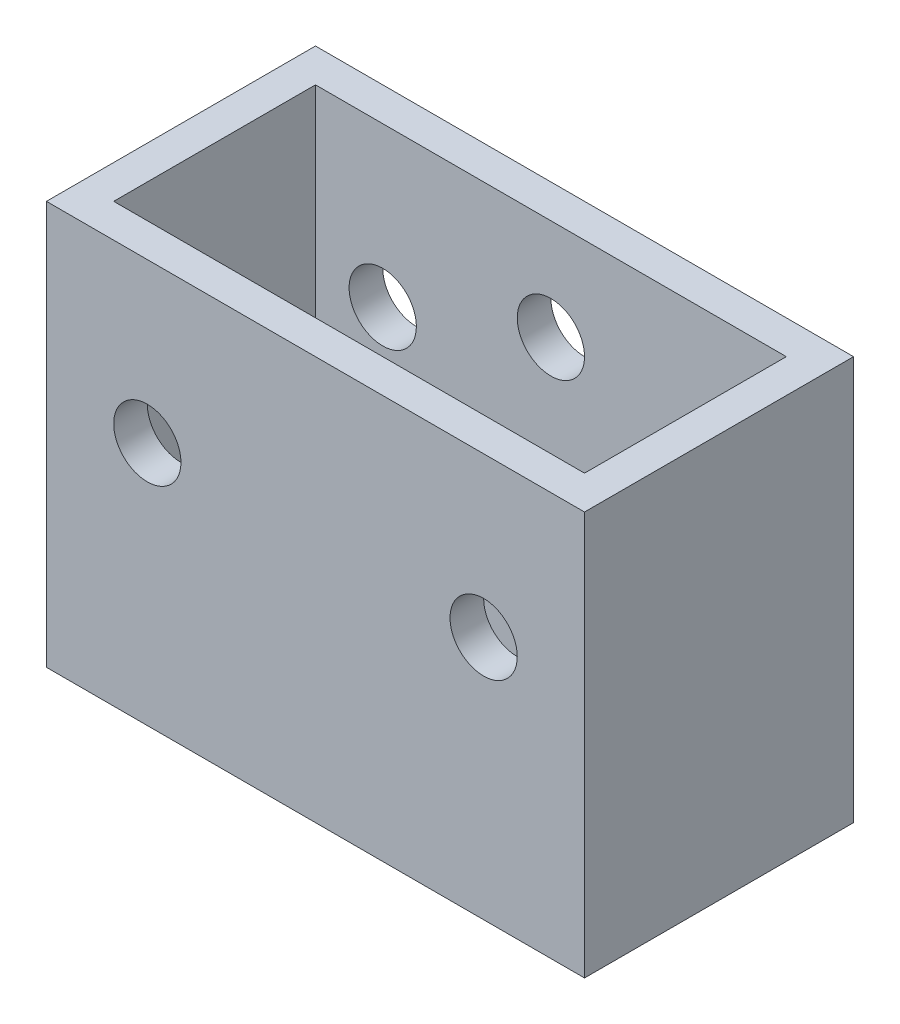
SolidWorks part; units mm, degrees
ref_plane "Front Plane" through (0, 0, 0) normal (0, 0, 1) x (1, 0, 0)
ref_plane "Top Plane" through (0, 0, 0) normal (0, 1, 0) x (1, 0, 0)
ref_plane "Right Plane" through (0, 0, 0) normal (1, 0, 0) x (0, 0, -1)
sketch "Sketch1" plane through (0, 0, 0) normal (0, 1, 0) x (1, 0, 0)
  line L1 (-25.4, 12.7) -> (25.4, 12.7)
  line L2 (-25.4, 12.7) -> (-25.4, -12.7)
  line L3 (-25.4, -12.7) -> (25.4, -12.7)
  line L4 (25.4, 12.7) -> (25.4, -12.7)
  line L5 (-25.4, 12.7) -> (25.4, -12.7) construction
  line L6 (-25.4, -12.7) -> (25.4, 12.7) construction
  line L7 (22.225, 9.525) -> (-22.225, 9.525)
  line L8 (22.225, 9.525) -> (22.225, -9.525)
  line L9 (22.225, -9.525) -> (-22.225, -9.525)
  line L10 (-22.225, 9.525) -> (-22.225, -9.525)
  line L11 (-19.05, 9.525) -> (19.05, -9.525) construction
  line L12 (-19.05, -9.525) -> (19.05, 9.525) construction
  line L13 (19.05, 9.525) -> (-19.05, -9.525) construction
  line L14 (19.05, -9.525) -> (-19.05, 9.525) construction
  line L15 (22.225, 9.525) -> (-22.225, -9.525) construction
  line L16 (22.225, -9.525) -> (-22.225, 9.525) construction
  point P0 (0, 0)
  point P6 (0, 0)
  point P11 (0, 0)
  point P16 (0, 0)
  dimension "D1" = 50.8
  dimension "D2" = 25.4
  dimension "D3" = 19.05
  dimension "D4" = 44.45
extrude "Boss-Extrude1" add sketch "Sketch1" along normal blind 38.1
sketch "Sketch2" plane through (0, 0, -12.7) normal (0, 0, -1) x (-1, 0, 0)
  line L2 (-25.4, 38.1) -> (25.4, 38.1) construction
  circle A0 centre (0, 28.575) radius 3.175
  circle A1 centre (0, 9.525) radius 3.175
  dimension "D1" = 6.35
  dimension "D2" = 19.05
  dimension "D3" = 9.525
extrude "Cut-Extrude1" cut sketch "Sketch2" against normal up to next
sketch "Sketch3" plane through (0, 0, 12.7) normal (0, 0, 1) x (1, 0, 0)
  line L0 (-25.4, 38.1) -> (25.4, 38.1) construction
  line L1 (25.4, 38.1) -> (25.4, 0) construction
  line L2 (-25.4, 38.1) -> (-25.4, 0) construction
  circle A0 centre (15.875, 23.1) radius 3.175
  circle A1 centre (-15.875, 23.1) radius 3.175
  dimension "D1" = 6.35
  dimension "D2" = 15
  dimension "D3" = 15
  dimension "D4" = 9.525
  dimension "D5" = 9.525
extrude "Cut-Extrude2" cut sketch "Sketch3" against normal through all
